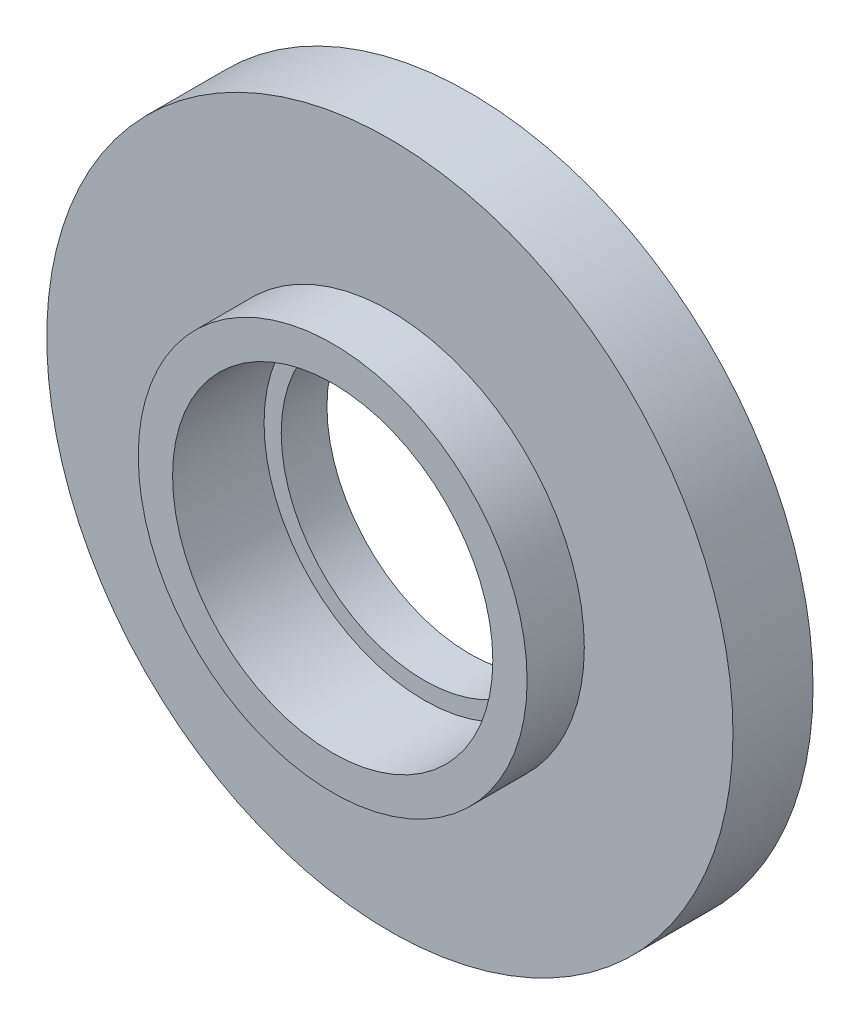
SolidWorks part; units mm, degrees
ref_plane "Front Plane" through (0, 0, 0) normal (0, 0, 1) x (1, 0, 0)
ref_plane "Top Plane" through (0, 0, 0) normal (0, 1, 0) x (1, 0, 0)
ref_plane "Right Plane" through (0, 0, 0) normal (1, 0, 0) x (0, 0, -1)
sketch "Sketch2" plane through (0, 0, 0) normal (0, 1, 0) x (1, 0, 0)
  line L0 (0, 0) -> (-30, 0)
  line L1 (-30, 0) -> (-30, -7)
  line L2 (-30, -7) -> (-17, -7)
  line L3 (-17, -7) -> (-17, -12)
  line L4 (-17, -12) -> (0, -12)
  line L5 (0, -12) -> (0, 0)
  dimension "D1" = 7
  dimension "D2" = 5
  dimension "D3" = 30
  dimension "D4" = 17
revolve "Revolve4" add sketch "Sketch2" angle 360 about L5
sketch "Sketch4" plane through (0, 0, 12) normal (0, 0, 1) x (1, 0, 0)
  circle A0 centre (0, 0) radius 14
  dimension "D1" = 28
extrude "Cut-Extrude1" cut sketch "Sketch4" against normal blind 8
sketch "Sketch5" plane through (0, 0, 0) normal (0, 0, -1) x (-1, 0, 0)
  circle A0 centre (0, 0) radius 12.5
  dimension "D1" = 25
extrude "Cut-Extrude4" cut sketch "Sketch5" against normal blind 8.1
sketch "Sketch7" plane through (0, 0, 0) normal (0, 0, -1) x (-1, 0, 0)
  circle A12 centre (0, 23) radius 2.5
  circle A18 centre (19.9186, 11.5) radius 2.5
  circle A19 centre (19.9186, -11.5) radius 2.5
  circle A20 centre (0, -23) radius 2.5
  circle A21 centre (-19.9186, -11.5) radius 2.5
  circle A22 centre (-19.9186, 11.5) radius 2.5
  point P14 (0, 0)
  point P15 (0, 0)
  point P16 (0, 0)
  dimension "D1" = 5
  dimension "D2" = 23
  dimension "D3" = 6
extrude "Cut-Extrude5" cut sketch "Sketch7" against normal blind 3
